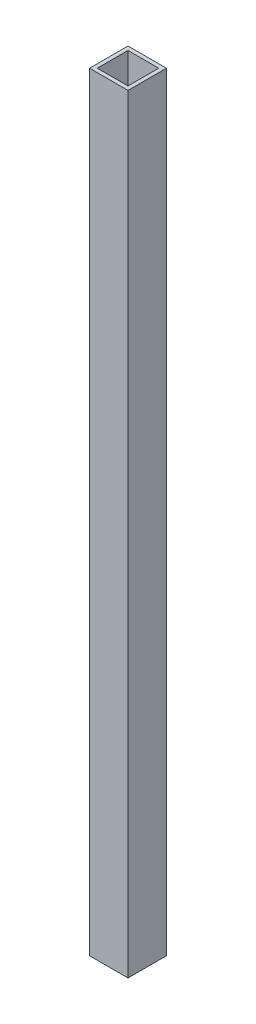
SolidWorks part; units mm, degrees
material "6061 Alloy"
ref_plane "Front Plane" through (0, 0, 0) normal (0, 0, 1) x (1, 0, 0)
ref_plane "Top Plane" through (0, 0, 0) normal (0, 1, 0) x (1, 0, 0)
ref_plane "Right Plane" through (0, 0, 0) normal (1, 0, 0) x (0, 0, -1)
sketch "Sketch1" plane through (0, 0, 0) normal (0, 1, 0) x (1, 0, 0)
  line L1 (0, 0) -> (15, 0)
  line L2 (0, 0) -> (0, 15)
  line L3 (0, 15) -> (15, 15)
  line L4 (15, 0) -> (15, 15)
  dimension "D1" = 15
extrude "Extrude-Thin1" add sketch "Sketch1" along normal blind 300 thin thin type one direction reverse wall 1.5
